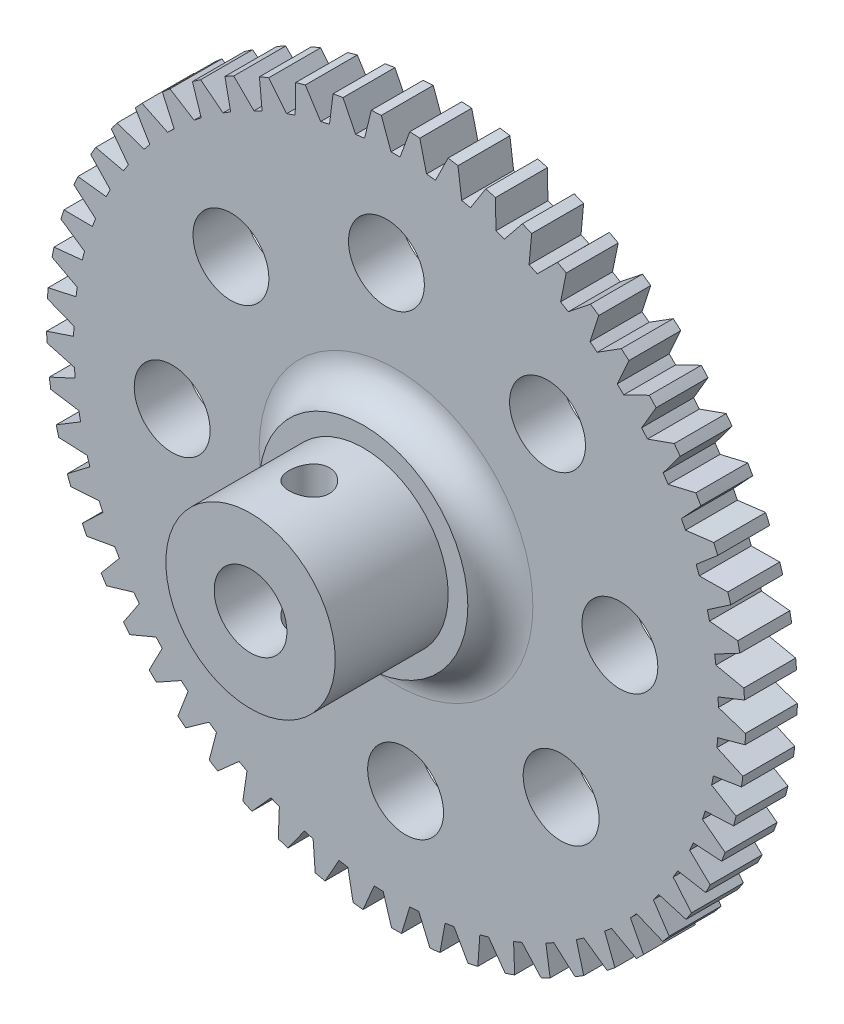
SolidWorks part; units mm, degrees
ref_plane "Front Plane" through (0, 0, 0) normal (0, 0, 1) x (1, 0, 0)
ref_plane "Top Plane" through (0, 0, 0) normal (0, 1, 0) x (1, 0, 0)
ref_plane "Right Plane" through (0, 0, 0) normal (1, 0, 0) x (0, 0, -1)
sketch "Sketch1" plane through (0, 0, 0) normal (0, 0, 1) x (1, 0, 0)
  circle A0 centre (0, 0) radius 19.645
  dimension "D1" = 39.29
extrude "Extrude1" add sketch "Sketch1" along normal blind 2.921
sketch "Sketch3" plane through (0, 0, 0) normal (0, 0, -1) x (-1, 0, 0)
  line L0 (0, 0) -> (0, -19.645) construction
  line L1 (0, 0) -> (2.1046, -19.5319) construction
  line L2 (0.7186, -18.1121) -> (0.254, -19.6434)
  line L3 (1.2259, -18.0848) -> (1.8519, -19.5575)
  line L4 (0, 0) -> (1.0538, -19.6167) construction
  line L5 (0, -19.645) -> (0.254, -19.6434) construction
  line L6 (1.8519, -19.5575) -> (2.1046, -19.5319) construction
  circle A0 centre (0, 0) radius 19.645 construction
  arc A1 (0.254, -19.6434) -> (1.8519, -19.5575) centre (0, 0) ccw
  arc A2 (0.7186, -18.1121) -> (1.2259, -18.0848) centre (0, 0) ccw
  dimension "D1" = 0.254
  dimension "D3" = 1.6002
  dimension "D4" = 1.6002
  dimension "D5" = 0.508
extrude "Cut-Extrude1" cut sketch "Sketch3" against normal through all
ref_axis "Axis1" through (0, 0, -18.3363) along (0, 0, 1)
pattern_circular "CirPattern1" count 57 over 360 about axis through (0, 0, -18.3363) along (0, 0, 1) of "Cut-Extrude1"
sketch "Sketch4" plane through (0, 0, 0) normal (0, 0, -1) x (-1, 0, 0)
  circle A0 centre (0, 0) radius 5.8674
  dimension "D1" = 11.7348
extrude "Extrude2" add sketch "Sketch4" along normal blind 1.8288
fillet "Fillet1" radius 1.8288 1 edges at (5.8674, 0, 0)
ref_plane "Plane1" through (0, 0, 1.4605) normal (0, 0, -1) x (-1, 0, 0)
sketch "Sketch5" plane through (0, 0, -1.8288) normal (0, 0, -1) x (-1, 0, 0)
  circle A0 centre (0, 0) radius 3.9116
  dimension "D1" = 7.8232
mirror "Mirror3" about plane through (0, 0, 1.4605) normal (0, 0, -1) of "Extrude2"
fillet "Fillet2" radius 1.8288 1 edges at (5.8674, 0, 2.921)
extrude "Cut-Extrude3" cut sketch "Sketch5" against normal through all
sketch "Sketch7" plane through (0, 0, 2.921) normal (0, 0, 1) x (1, 0, 0)
  line L0 (0, 0) -> (-14.4725, 13.2843) construction
  circle A0 centre (-9.2813, 8.5192) radius 2.1336
  arc A1 (-14.2801, 13.491) -> (-14.662, 13.0748) centre (0, 0) ccw construction
  point P8 (-14.4725, 13.2843)
  dimension "D1" = 4.2672
  dimension "D3" = 12.5984
extrude "Cut-Extrude4" cut sketch "Sketch7" against normal up to surface (2.921 mm away) up to face at (7.6962, 0, 0)
pattern_circular "CirPattern2" count 8 every 45 about axis through (0, 0, -1.8288) along (0, 0, -1) of "Cut-Extrude4"
sketch "Sketch8" plane through (0, 0, 4.7498) normal (0, 0, 1) x (1, 0, 0)
  circle A0 centre (0, 0) radius 2.045
  circle A1 centre (0, 0) radius 4.7625
  dimension "D1" = 9.525
  dimension "D2" = 4.09
extrude "Boss-Extrude1" add sketch "Sketch8" along normal blind 6.35 and the other way up to surface (6.5786 mm away) other way up to face at (-3.9116, 0, -1.8288)
hole_wizard "#4-40 Tapped Hole1" positions "3DSketch1" profile "Sketch11" tap size "#4-40" standard "Ansi Inch" end condition through all
sketch3d "3DSketch1"
  point P0 (0, 4.7625, 7.7978)
  dimension "D1" = 3.302
sketch "Sketch11" plane through (0, 4.7625, 7.7978) normal (1, 0, 0) x (0, 0, 1)
  line L0 (0, 0) -> (0, 24.4075)
  line L1 (0, 24.4075) -> (1.1303, 24.4075)
  line L2 (1.1303, 24.4075) -> (1.1303, 0)
  line L5 (1.1303, 0) -> (0, 0)
  line L11 (0, -6.35) -> (0, 107.95) construction
  dimension "Thread Major Dia." = 2.2606
  dimension "Thru Tap Drill Depth" = 24.4075
sketch "Sketch12" plane through (0, 0, 2.921) normal (0, 0, 1) x (1, 0, 0)
  circle A0 centre (0, 0) radius 18.13
  dimension "D1" = 36.26
